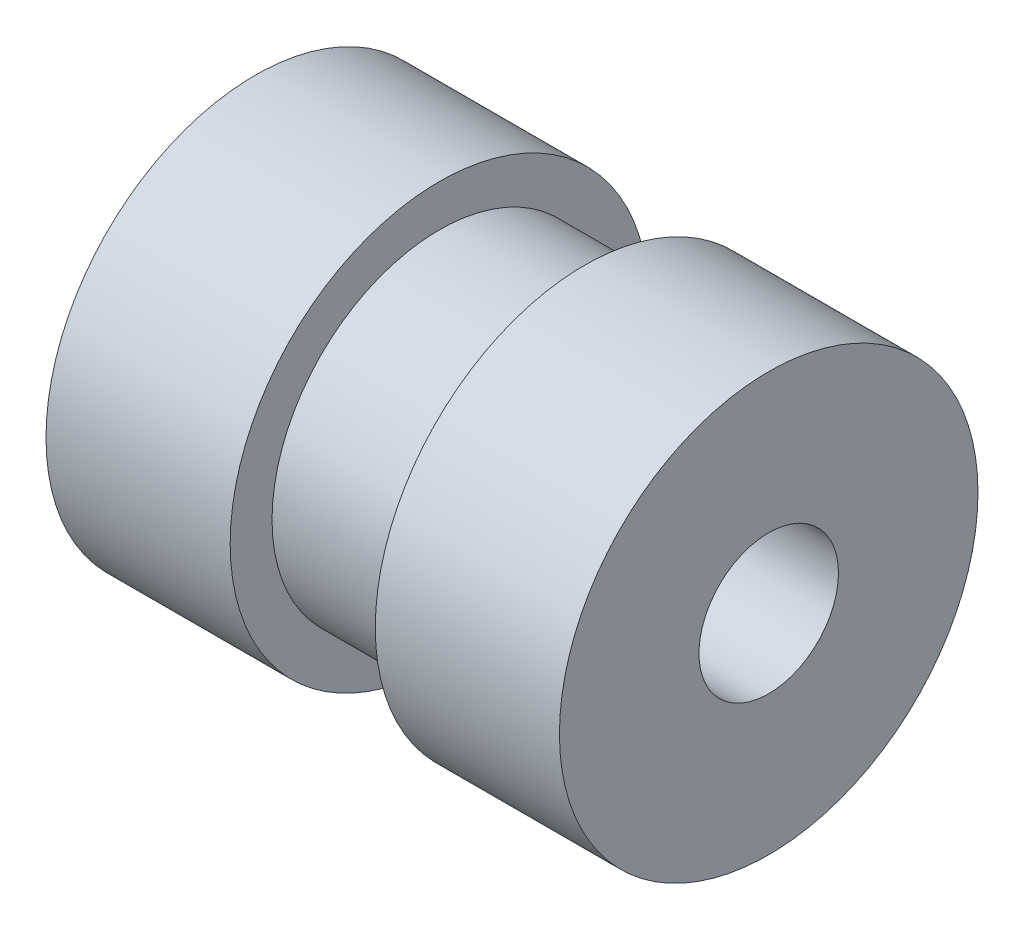
SolidWorks part; units mm, degrees
material "Silicon Rubber"
ref_plane "Front Plane" through (0, 0, 0) normal (0, 0, 1) x (1, 0, 0)
ref_plane "Top Plane" through (0, 0, 0) normal (0, 1, 0) x (1, 0, 0)
ref_plane "Right Plane" through (0, 0, 0) normal (1, 0, 0) x (0, 0, -1)
sketch "Sketch1" plane through (0, 0, 0) normal (1, 0, 0) x (0, 0, -1)
  circle A0 centre (0, 0) radius 3.175
  circle A1 centre (0, 0) radius 9.525
  dimension "D1" = 6.35
  dimension "D2" = 19.05
extrude "Boss-Extrude1" add sketch "Sketch1" along normal blind 8.382
sketch "Sketch2" plane through (8.382, 0, 0) normal (1, 0, 0) x (0, 0, -1)
  circle A0 centre (0, 0) radius 3.175
  circle A1 centre (0, 0) radius 7.62
  dimension "D1" = 15.24
extrude "Boss-Extrude2" add sketch "Sketch2" along normal blind 6.604
sketch "Sketch3" plane through (14.986, 0, 0) normal (1, 0, 0) x (0, 0, -1)
  circle A0 centre (0, 0) radius 3.175
  circle A1 centre (0, 0) radius 9.525
extrude "Boss-Extrude3" add sketch "Sketch3" along normal blind 8.382
